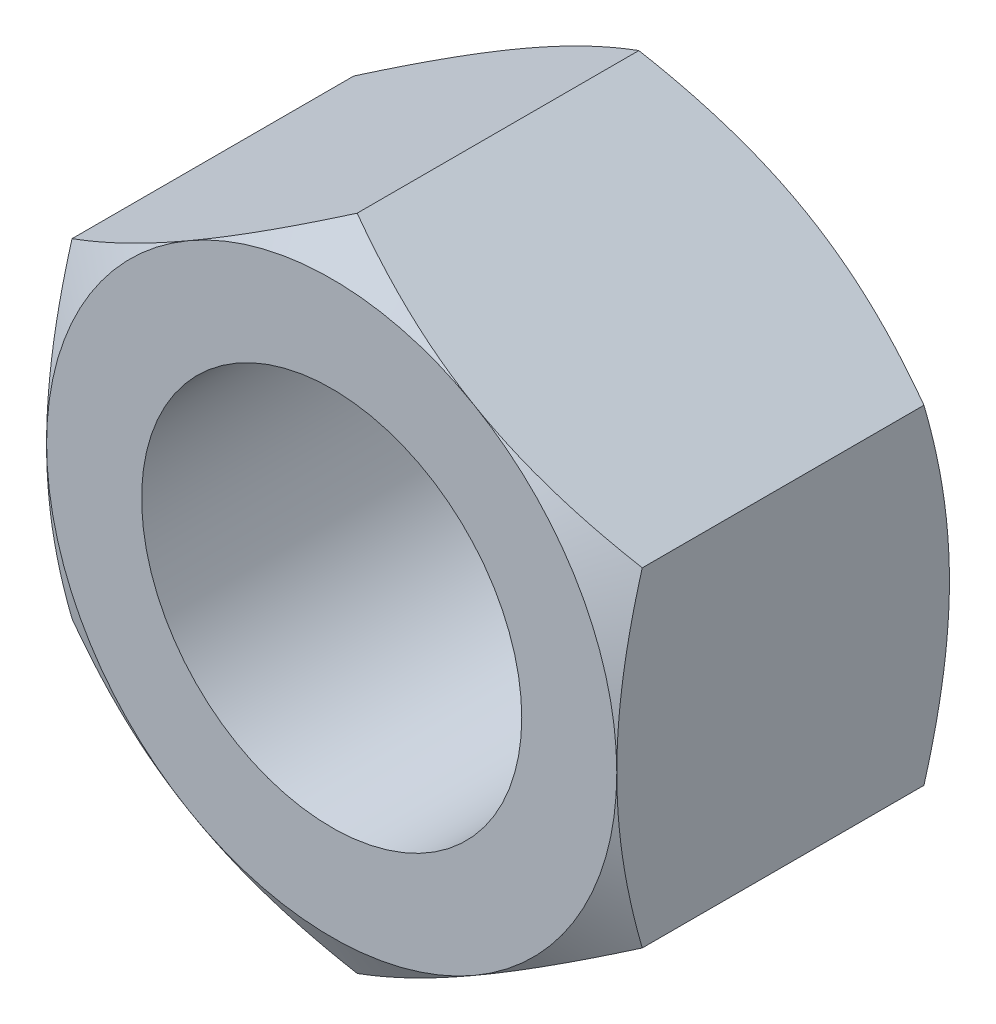
SolidWorks part; units mm, degrees
ref_plane "Front" through (0, 0, 0) normal (0, 0, 1) x (1, 0, 0)
ref_plane "Top" through (0, 0, 0) normal (0, 1, 0) x (1, 0, 0)
ref_plane "Right" through (0, 0, 0) normal (1, 0, 0) x (0, 0, -1)
sketch "Sketch1" plane through (0, 0, 0) normal (0, 0, 1) x (1, 0, 0)
  line L1 (-7.1437, 4.1244) -> (-7.1437, -4.1244)
  line L2 (-7.1437, -4.1244) -> (0, -8.2489)
  line L3 (0, -8.2489) -> (7.1438, -4.1244)
  line L4 (7.1438, -4.1244) -> (7.1437, 4.1244)
  line L5 (7.1437, 4.1244) -> (0, 8.2489)
  line L6 (0, 8.2489) -> (-7.1437, 4.1244)
  circle A0 centre (0, 0) radius 7.1438 construction
  circle A1 centre (0, 0) radius 4.7625
  point P10 (0, 4.7625)
  dimension "hex" = 14.2875
  dimension "dia" = 9.525
extrude "Extrude1" add sketch "Sketch1" along normal mid plane 8.3344
sketch "Sketch4" plane through (0, 0, -4.1672) normal (0, 0, -1) x (-1, 0, 0)
  circle A0 centre (0, 0) radius 4.7625 construction
  circle A1 centre (0, 0) radius 4.7625
curve "Helix/Spiral3" [suppressed] pitch 1.5875 height 10.0012 turns 6.3
sketch "Sketch3" plane through (0, 0, 0) normal (1, 0, 0) x (0, 0, -1)
  line L0 (4.1672, 4.7625) -> (5.5562, 4.7625)
  line L1 (5.5562, 4.7625) -> (4.9609, 3.7314)
  line L2 (4.9609, 3.7314) -> (4.7625, 3.7314)
  line L3 (4.7625, 3.7314) -> (4.1672, 4.7625)
  line L4 (4.4648, 4.2469) -> (5.2586, 4.2469) construction
  dimension "D1" = 60
  dimension "D2" = 0.7937
  dimension "D3" = 0.1984
sweep "Sweep1" [suppressed] add profiles "Sketch3" path "Helix/Spiral3"
sketch "Sketch6" [suppressed] plane through (0, 0, 0) normal (1, 0, 0) x (0, 0, -1)
  line L0 (-4.5641, 5.1594) -> (-3.7703, 4.3656)
  line L1 (-3.7703, 4.3656) -> (-3.7703, 0) construction
  line L2 (5.8287, 0) -> (-5.8287, 0) construction
  line L3 (-3.7703, 0) -> (-5.8336, 0)
  line L4 (-5.8336, 0) -> (-5.8336, 5.1594)
  line L5 (-5.8336, 5.1594) -> (-4.5641, 5.1594)
  line L6 (-3.7703, 4.3656) -> (0.5953, 0)
  line L7 (0.5953, 0) -> (-3.7703, 0)
  line L8 (-4.1672, -4.1244) -> (-4.1672, 4.1244) construction
  point P2 (-4.1672, 4.7625)
  dimension "D2" = 0.7937
  dimension "D1" = 45
revolve "Cut-Revolve1" [suppressed] cut sketch "Sketch6" angle 360 about L3
sketch "Sketch7" plane through (0, 0, 4.1672) normal (0, 0, 1) x (1, 0, 0)
  circle A0 centre (0, 0) radius 7.1438 construction
  circle A1 centre (0, 0) radius 7.1438
extrude "Extrude2" cut sketch "Sketch7" against normal blind 25.4 draft 60 flip side to cut
mirror "Mirror1" about plane through (0, 0, 0) normal (0, 0, 1) of "Extrude2", "Cut-Revolve1"
sketch "Sketch8" [suppressed] plane through (0, 0, 4.1672) normal (0, 0, 1) x (1, 0, 0)
  line L0 (-3.3676, 3.3676) -> (0, 0) construction
  line L1 (0, -5.8287) -> (0, 5.8287) construction
  circle A0 centre (0, 0) radius 4.7625 construction
  point P0 (-3.3676, 3.3676)
  dimension "D1" = 45
equation "\"D3@Helix/Spiral3\" = \"length@Extrude1\" * 1.2"
equation "\"D2@Sketch3\" = \"D4@Helix/Spiral3\" * .5"
equation "\"D3@Sketch3\" = \"D4@Helix/Spiral3\" * .125"
equation "\"D2@Sketch6\" = \"D4@Helix/Spiral3\" * .5"
